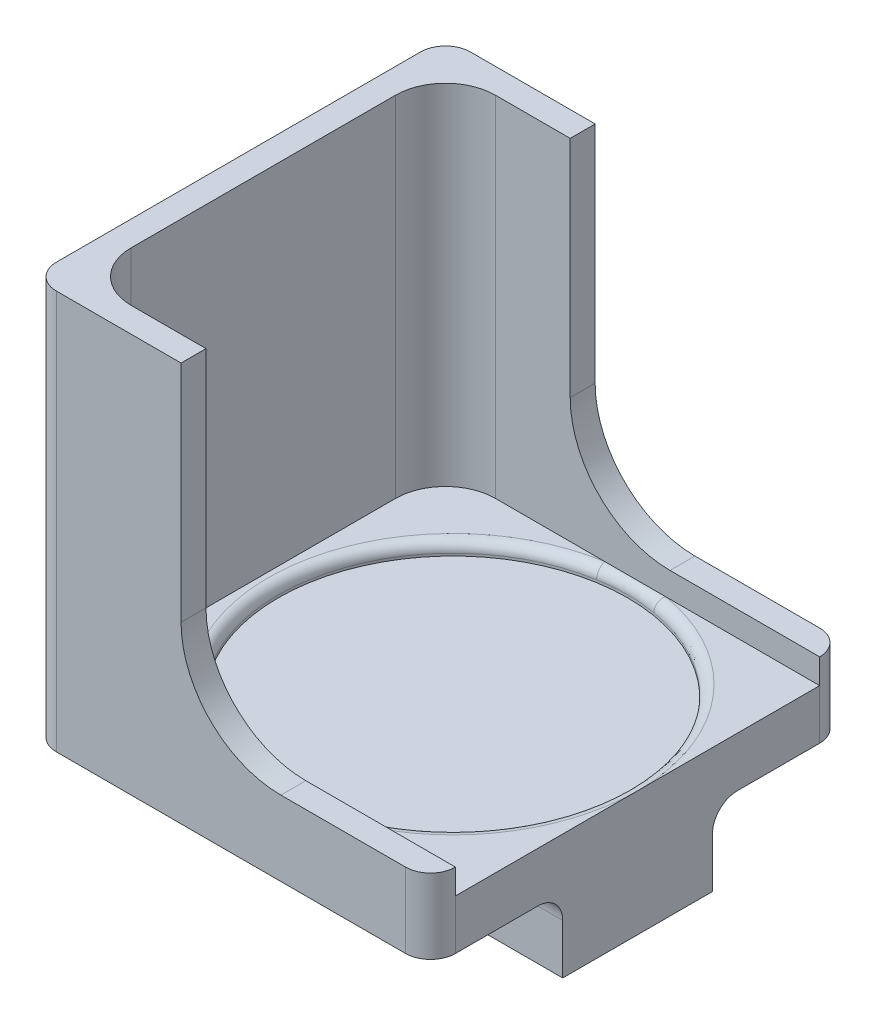
SolidWorks part; units mm, degrees
ref_plane "前基準面" through (0, 0, 0) normal (0, 0, 1) x (1, 0, 0)
ref_plane "上基準面" through (0, 0, 0) normal (0, 1, 0) x (1, 0, 0)
ref_plane "右基準面" through (0, 0, 0) normal (1, 0, 0) x (0, 0, -1)
sketch "草圖2" plane through (0, 0, 0) normal (0, 1, 0) x (1, 0, 0)
  line L1 (-35, 41.5) -> (35, 41.5)
  line L2 (-40, 36.5) -> (-40, -36.5)
  line L3 (-35, -41.5) -> (35, -41.5)
  line L4 (40, 36.5) -> (40, -36.5)
  line L5 (-40, 41.5) -> (40, -41.5) construction
  line L6 (-40, -41.5) -> (40, 41.5) construction
  arc A0 (35, 41.5) -> (40, 36.5) centre (35, 36.5) cw
  arc A1 (35, -41.5) -> (40, -36.5) centre (35, -36.5) ccw
  arc A2 (-40, -36.5) -> (-35, -41.5) centre (-35, -36.5) ccw
  arc A3 (-35, 41.5) -> (-40, 36.5) centre (-35, 36.5) ccw
  point P0 (0, 0)
  dimension "D3" = 5
  dimension "D1" = 80
  dimension "D2" = 83
extrude "填料-伸長1" add sketch "草圖2" along normal blind 10
sketch "草圖3" plane through (0, 10, 0) normal (0, 1, 0) x (1, 0, 0)
  line L0 (0, -45.9482) -> (0, 50.4274) construction
  line L1 (64.5067, 0) -> (-60.7671, 0) construction
  line L2 (-25, -36.5) -> (40, -36.5)
  line L4 (35, 41.5) -> (-35, 41.5) construction
  line L7 (35, 41.5) -> (-35, 41.5)
  line L8 (-40, 36.5) -> (-40, -36.5)
  line L9 (-35, -41.5) -> (35, -41.5)
  line L10 (40, -36.5) -> (40, 36.5)
  line L12 (-40, 36.5) -> (-40, -36.5)
  line L13 (-35, -41.5) -> (35, -41.5)
  line L15 (-35, -26.5) -> (-35, 26.5)
  line L18 (-25, 36.5) -> (40, 36.5)
  line L19 (35, 41.5) -> (-35, 41.5)
  arc A2 (-35, 41.5) -> (-40, 36.5) centre (-35, 36.5) ccw construction
  arc A3 (-35, 41.5) -> (-40, 36.5) centre (-35, 36.5) ccw
  arc A4 (-25, -36.5) -> (-35, -26.5) centre (-25, -26.5) cw
  circle A5 centre (0, 0) radius 35 construction
  arc A6 (40, 36.5) -> (35, 41.5) centre (35, 36.5) ccw
  arc A7 (-35, 41.5) -> (-40, 36.5) centre (-35, 36.5) ccw
  arc A8 (-40, -36.5) -> (-35, -41.5) centre (-35, -36.5) ccw
  arc A9 (35, -41.5) -> (40, -36.5) centre (35, -36.5) ccw
  arc A12 (-40, -36.5) -> (-35, -41.5) centre (-35, -36.5) ccw
  arc A13 (35, -41.5) -> (40, -36.5) centre (35, -36.5) ccw
  arc A18 (-25, 36.5) -> (-35, 26.5) centre (-25, 26.5) ccw
  arc A19 (35, 41.5) -> (40, 36.5) centre (35, 36.5) cw
  point P12 (-40, 25)
  point P17 (45, 35)
  point P32 (0, 35)
  point P34 (-35, 0)
  point P42 (-35, 35)
  dimension "D1" = 10
  dimension "D3" = 70
  dimension "D2" = 0
extrude "填料-伸長2" add sketch "草圖3" along normal blind 70
sketch "草圖5" plane through (0, 10, 0) normal (0, 1, 0) x (1, 0, 0)
  line L0 (-49.8846, 0) -> (51.8846, 0) construction
  line L1 (3, 0) -> (51.8846, 0) construction
  line L4 (40, -36.5) -> (40, 36.5) construction
  circle A0 centre (3, 0) radius 35
  point P4 (3.011, 0)
  point P5 (-8.2866, 0)
  point P11 (12.0348, 0)
  dimension "D1" = 70
  dimension "D2" = 37
extrude "除料-伸長3" cut sketch "草圖5" against normal blind 2.5
sketch "草圖6" plane through (0, 0, 0) normal (0, -1, 0) x (1, 0, 0)
  line L7 (-40, -36.5) -> (-40, 36.5) construction
  line L8 (40, 15) -> (-40, 15)
  line L9 (40, 15) -> (40, -15)
  line L10 (40, -15) -> (-40, -15)
  line L11 (-40, 15) -> (-40, -15)
  line L12 (40, 15) -> (-40, -15) construction
  line L13 (40, -15) -> (-40, 15) construction
  point P0 (0, 0)
  point P8 (0, 0)
  dimension "D1" = 30
extrude "填料-伸長3" add sketch "草圖6" along normal blind 15
sketch "草圖7" plane through (0, 0, 36.5) normal (0, 0, -1) x (-1, 0, 0)
  line L1 (-35, 80) -> (35, 80) construction
  line L2 (10, 80) -> (-40, 80)
  line L3 (-40, 80) -> (-40, 15)
  line L4 (40, 80) -> (40, 0) construction
  line L6 (-40, 80) -> (-40, 10) construction
  line L7 (40, -15) -> (-40, -15) construction
  line L8 (10, 80) -> (10, 35)
  line L9 (-10, 15) -> (-40, 15)
  arc A0 (10, 35) -> (-10, 15) centre (-10, 35) cw
  point P9 (10, 80)
  point P11 (10, 25)
  point P15 (-40, 80)
  dimension "D3" = 20
  dimension "D1" = 30
  dimension "D2" = 30
extrude "除料-伸長4" cut sketch "草圖7" against normal through all and the other way through all
fillet "圓角1" radius 2 1 edges at (3, 10, 35)
sketch "草圖8" plane through (0, -15, 0) normal (0, -1, 0) x (1, 0, 0)
  line L0 (-50.5753, 0) -> (52.502, 0) construction
  line L1 (40, -15) -> (40, 15) construction
  circle A0 centre (35, 0) radius 3
  point P5 (26.7327, 0)
  dimension "D1" = 6
  dimension "D2" = 5
extrude "除料-伸長5" cut sketch "草圖8" against normal blind 10
fillet "圓角2" radius 5 2 edges at (0, 0, 15) (0, 0, -15)
